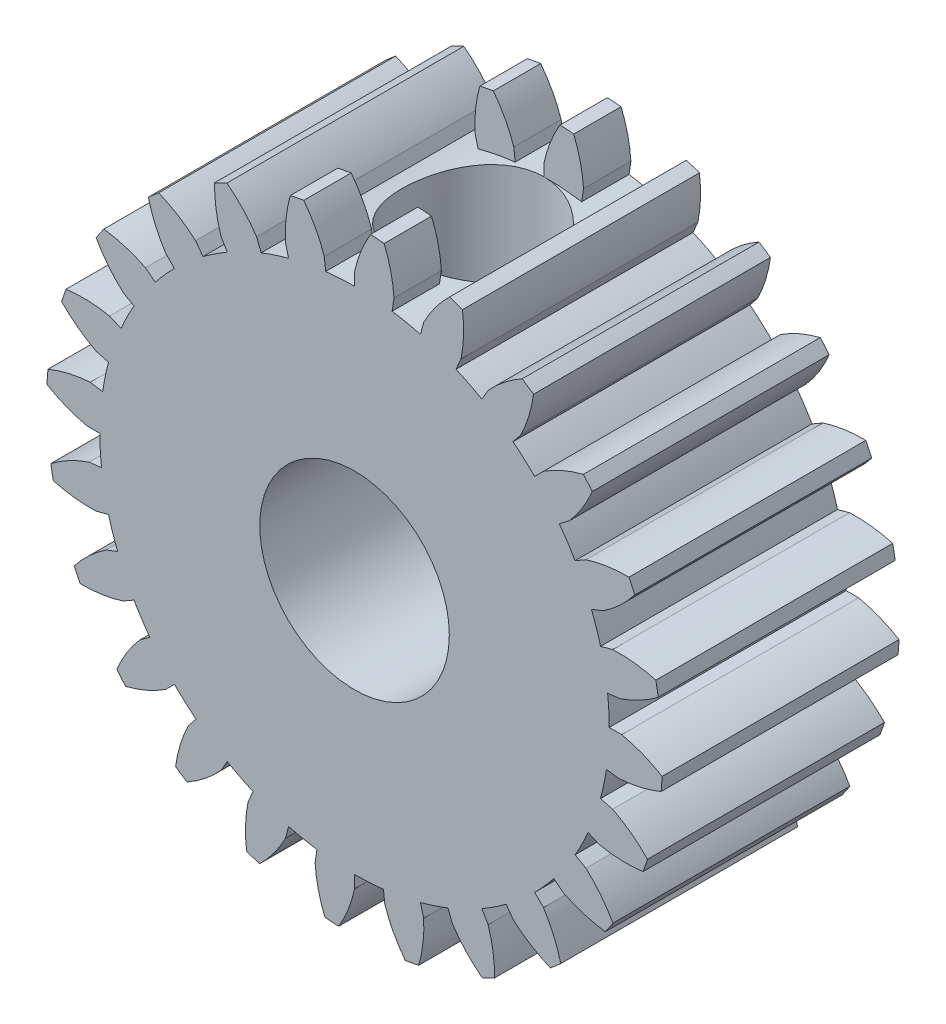
SolidWorks part; units mm, degrees
ref_plane "Front Plane" through (0, 0, 0) normal (0, 0, 1) x (1, 0, 0)
ref_plane "Top Plane" through (0, 0, 0) normal (0, 1, 0) x (1, 0, 0)
ref_plane "Right Plane" through (0, 0, 0) normal (1, 0, 0) x (0, 0, -1)
sketch "Gear" plane through (0, 0, 0) normal (0, 0, 1) x (1, 0, 0)
  circle A0 centre (0, 0) radius 6
  circle A1 centre (0, 0) radius 6.5
  circle A2 centre (0, 0) radius 5.375
  circle A3 centre (0, 0) radius 5.5
  circle A4 centre (0, 0) radius 5.6382
  dimension "Pitch" = 12
  dimension "Addendum" = 13
  dimension "Root" = 10.75
  dimension "Clearance" = 11
  dimension "Base" = 11.2763
sketch "Involute" plane through (0, 0, 0) normal (0, 0, 1) x (1, 0, 0)
  line L0 (0, 0) -> (0, 5.6382)
  line L1 (0, 0) -> (2.8191, 4.8828) construction
  line L2 (0, 0) -> (4.8828, 2.8191) construction
  line L3 (0, 0) -> (5.6382, 0) construction
  line L4 (5.6382, 0) -> (5.6382, 8.8564) construction
  line L5 (4.8828, 2.8191) -> (1.9307, 7.9323) construction
  line L6 (2.8191, 4.8828) -> (0.2625, 6.3589) construction
  line L7 (0, 0) -> (0.7832, 5.9487) construction
  line L8 (0, 0) -> (1.5529, 5.7956)
  line L9 (0.444, 5.9836) -> (0, 0) construction
  circle A0 centre (0, 0) radius 5.6382 construction
  circle A1 centre (0, 0) radius 6 construction
  arc A3 (0.7832, 5.9487) -> (0.1034, 5.9991) centre (0, 0) ccw
  spline S0 degree 3 poles (0, 5.6382) (0.496, 7.9471) (3.7355, 8.8594) (5.6382, 8.8564) knots 0 0 0 0 1 1 1 1
  spline S1 degree 3 poles (0.8321, 5.5764) (0.6823, 7.9332) (-2.3871, 9.3137) (-4.2693, 9.5915) knots 0 0 0 0 1 1 1 1
  point P10 (0, 0)
  dimension "Involute Control" = 90
  dimension "Base Circle Quarter Circumference" = 8.8564
  dimension "D1" = 5.9043
  dimension "D2" = 2.9521
  dimension "Circular Pitch" = 15
  dimension "Involute Array" = 4
sketch "Sketch3" plane through (0, 0, 0) normal (0, 0, 1) x (1, 0, 0)
  line L0 (0.8321, 5.5764) -> (0.7933, 5.3161)
  line L2 (0, 5.6382) -> (0, 5.375)
  arc A2 (0.3368, 6.4913) -> (0, 5.6382) centre (2.7472, 5.0468) ccw
  circle A10 centre (0, 0) radius 5.375 construction
  circle A11 centre (0, 0) radius 5.6382 construction
  arc A17 (0.8321, 5.5764) -> (0.625, 6.4699) centre (-1.9723, 5.3969) ccw
  arc A18 (0.7933, 5.3161) -> (0, 5.375) centre (0, 0) ccw
  arc A19 (0.625, 6.4699) -> (0.3368, 6.4913) centre (0, 0) ccw
  circle A20 centre (0, 0) radius 6.5 construction
  spline S1 degree 3 poles (0.8321, 5.5764) (0.6823, 7.9332) (-2.3871, 9.3137) (-4.2693, 9.5915) knots 0 0 0 0 1 1 1 1 construction
  spline S2 degree 3 poles (0, 5.6382) (0.496, 7.9471) (3.7355, 8.8594) (5.6382, 8.8564) knots 0 0 0 0 1 1 1 1 construction
extrude "Boss-Extrude1" add sketch "Sketch3" along normal blind 5
ref_axis "Axis1" through (0, 0, 0) along (0, 0, 1)
pattern_circular "CirPattern1" count 24 over 360 about axis through (0, 0, 0) along (0, 0, 1) of bodies 101
sketch "Sketch6" plane through (0, 0, 0) normal (0, 0, 1) x (1, 0, 0)
  circle A0 centre (0, 0) radius 5.375 construction
  circle A1 centre (0, 0) radius 5.375
  circle A2 centre (0, 0) radius 2
  dimension "D1" = 4
extrude "Boss-Extrude3" add sketch "Sketch6" along normal up to surface (5 mm away) up to face at (-1.0887, 5.7311, 5)
sketch "Sketch7" plane through (0, 0, 0) normal (0, 1, 0) x (1, 0, 0)
  line L0 (0, -5) -> (0, 0) construction
  circle A0 centre (0, -2.5) radius 1.5
  dimension "D1" = 3
extrude "Cut-Extrude1" cut sketch "Sketch7" along normal up to surface (6.5 mm away) up to face at (0.4809, 6.4814, 2.5)
sketch "Sketch8" plane through (0, 0, 0) normal (0, 1, 0) x (1, 0, 0)
  line L1 (-1.5, -4) -> (1.5, -4)
  line L2 (-1.5, -4) -> (-1.5, -1)
  line L3 (-1.5, -1) -> (1.5, -1)
  line L4 (1.5, -4) -> (1.5, -1)
  line L5 (-1.5, -4) -> (1.5, -1) construction
  line L6 (-1.5, -1) -> (1.5, -4) construction
  line L7 (-6.4699, -5) -> (-6.4699, 0) construction
  point P0 (0, -2.5)
  point P10 (-6.4699, -2.5)
  dimension "D1" = 3
extrude "Cut-Extrude2" cut sketch "Sketch8" along direction (0, 1, 0) on the side against the normal up to surface (4.8385 mm away) from offset 10 up to face at (1.101, 5.2566, 0.7728)
equation "\"Module\"= .5"
equation "\"Teeth\"= 24"
equation "\"Pressure Angle\"= 20deg"
equation "\"Pitch@Gear\"= \"Module\" * \"Teeth\""
equation "\"Addendum@Gear\" = \"Pitch@Gear\" +  ( \"Module\" * 2 ) "
equation "\"Clearance@Gear\" = \"Pitch@Gear\" - ( \"Module\" * 2 )"
equation "\"Root@Gear\"= \"Pitch@Gear\" - ( ( \"Module\" * 1.25 ) * 2 )"
equation "\"Base@Gear\"= \"Pitch@Gear\" * cos ( \"Pressure Angle\" )"
equation "\"Circular Pitch@Involute\"=360/\"Teeth\""
equation "\"Base Circle Quarter Circumference@Involute\"= \"Base@Gear\" * pi / 4"
equation "\"D1@Involute\"= \"Base Circle Quarter Circumference@Involute\" / 3 * 2"
equation "\"D2@Involute\"= \"Base Circle Quarter Circumference@Involute\" / 3"
equation "\"D1@CirPattern1\"= \"Teeth\""
